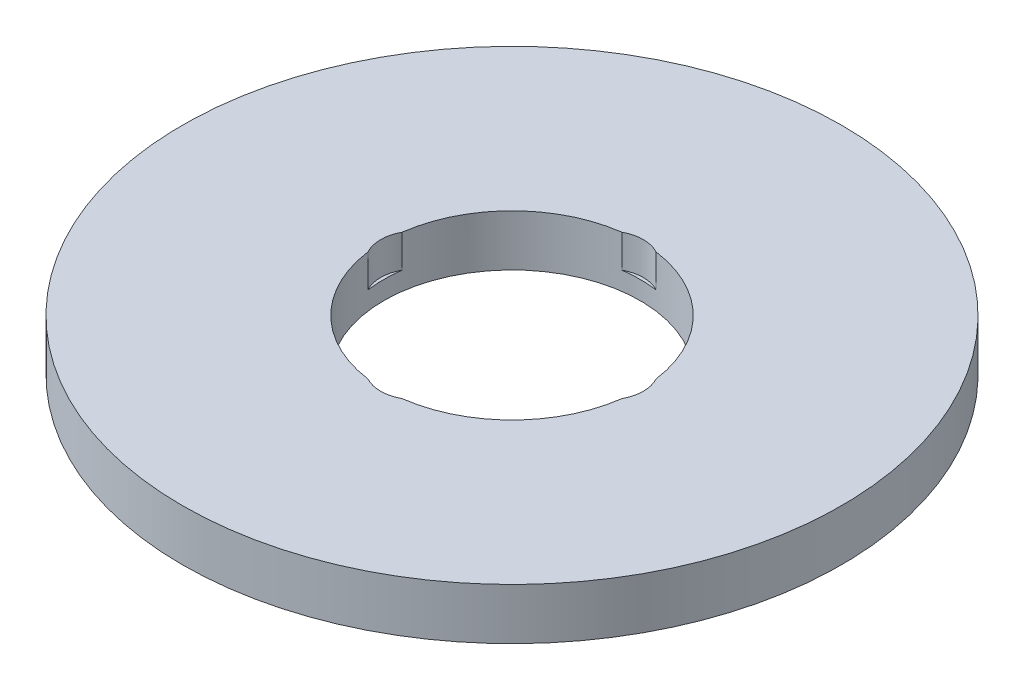
SolidWorks part; units mm, degrees
ref_plane "Front Plane" through (0, 0, 0) normal (0, 0, 1) x (1, 0, 0)
ref_plane "Top Plane" through (0, 0, 0) normal (0, 1, 0) x (1, 0, 0)
ref_plane "Right Plane" through (0, 0, 0) normal (1, 0, 0) x (0, 0, -1)
sketch "Sketch1" plane through (0, 0, 0) normal (0, 1, 0) x (1, 0, 0)
  circle A0 centre (0, 0) radius 90
  dimension "FLANGE_OD" = 180
extrude "Boss-Extrude1" add sketch "Sketch1" along normal blind 14
sketch "Sketch2" plane through (0, 0, 0) normal (0, 1, 0) x (1, 0, 0)
  circle A0 centre (0, 0) radius 35
  dimension "BORE_D" = 70
extrude "Cut-Extrude1" cut sketch "Sketch2" along normal through all
sketch "Sketch3" plane through (0, 14, 0) normal (0, 1, 0) x (1, 0, 0)
  circle A0 centre (0, 0) radius 25.9934 construction
  circle A1 centre (-25.9934, 0) radius 9.8727
  dimension "BOLT_D" = 19.7453
  dimension "BOLT_PCD" = 51.9868
extrude "Cut-Extrude2" cut sketch "Sketch3" against normal blind 8.9719
pattern_circular "CirPattern1" count 4 over 360 about axis through (0, 0, 0) along (0, 1, 0) of "Cut-Extrude2"
